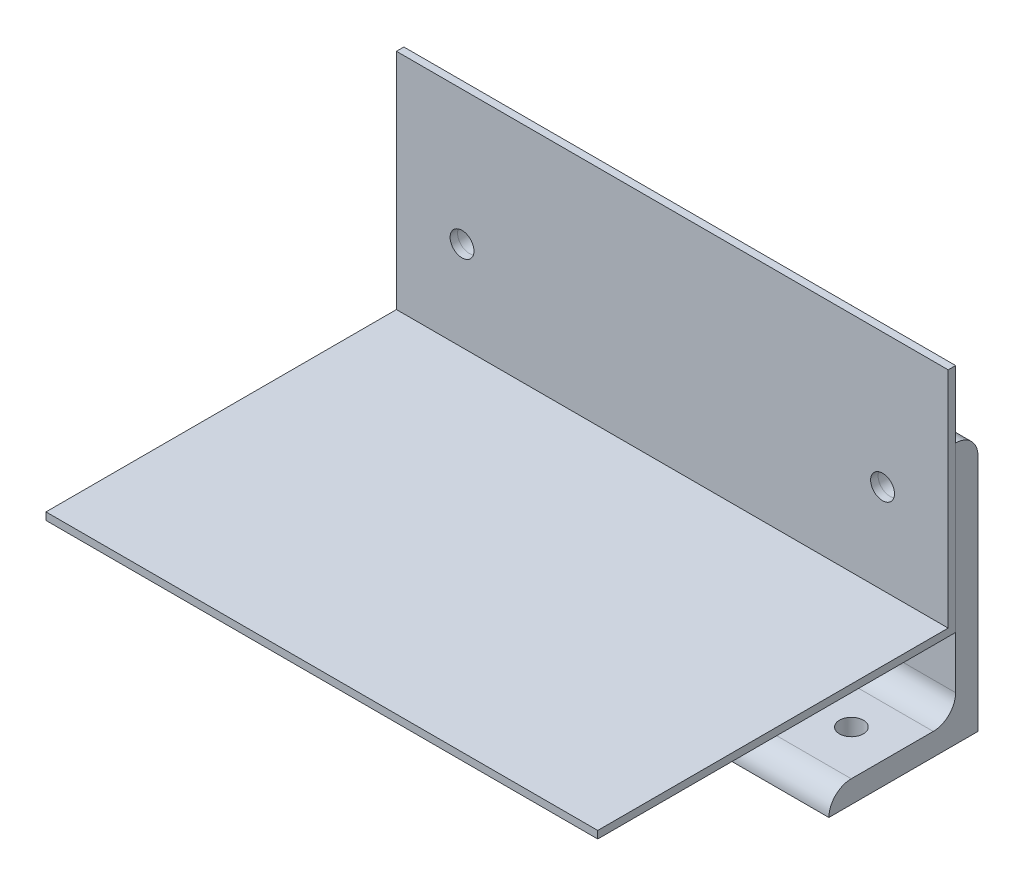
SolidWorks part; units mm, degrees
ref_plane "Спереди" through (0, 0, 0) normal (0, 0, 1) x (1, 0, 0)
ref_plane "Сверху" through (0, 0, 0) normal (0, 1, 0) x (1, 0, 0)
ref_plane "Справа" through (0, 0, 0) normal (1, 0, 0) x (0, 0, -1)
sketch "Эскиз1" plane through (0, 0, 0) normal (1, 0, 0) x (0, 0, -1)
  line L1 (0, 0) -> (-48, 0)
  line L2 (0, 0) -> (0, 31)
  line L3 (0, 31) -> (-1, 31)
  line L4 (-48, 0) -> (-48, 1)
  line L7 (-48, 1) -> (-1, 1)
  line L8 (-1, 31) -> (-1, 1)
  dimension "D1" = 1
  dimension "D2" = 31
  dimension "D3" = 48
  dimension "D4" = 1
extrude "Бобышка-Вытянуть1" add sketch "Эскиз1" along normal blind 74
sketch "Эскиз2" plane through (0, 0, 0) normal (0, 0, -1) x (-1, 0, 0)
  line L0 (-74, 31) -> (0, 31) construction
  line L1 (-74, 0) -> (-74, 31) construction
  line L2 (0, 0) -> (0, 31) construction
  circle A0 centre (-65.2, 13) radius 1.6
  circle A1 centre (-8.8, 13) radius 1.6
  dimension "D1" = 3.2
  dimension "D2" = 3.2
  dimension "D3" = 18
  dimension "D4" = 8.8
  dimension "D5" = 8.8
extrude "Вырез-Вытянуть1" cut sketch "Эскиз2" against normal blind 13
sketch "Sketch2" plane through (0, 0, 0) normal (0, 0, -1) x (-1, 0, 0)
  line L0 (-74, 0) -> (-74, 31) construction
  line L1 (-74, 22) -> (0, 22)
  line L2 (-74, 22) -> (-74, -10)
  line L3 (-74, -10) -> (0, -10)
  line L4 (0, 22) -> (0, -10)
  line L5 (0, 0) -> (0, 31) construction
  line L6 (-74, 0) -> (0, 0) construction
  circle A0 centre (-65.2, 13) radius 1.6 construction
  dimension "D1" = 9
  dimension "D2" = 10
extrude "Boss-Extrude1" add sketch "Sketch2" along normal blind 3 separate body
sketch "Sketch3" plane through (0, -10, 0) normal (0, -1, 0) x (1, 0, 0)
  line L0 (74, 48) -> (74, 0) construction
  line L1 (0, -3) -> (74, -3)
  line L2 (0, -3) -> (0, 17)
  line L3 (0, 17) -> (74, 17)
  line L4 (74, -3) -> (74, 17)
  circle A0 centre (6, 7.9797) radius 1.6
  circle A1 centre (68, 7.9797) radius 1.6
  dimension "D2" = 3.2
  dimension "D4" = 6
  dimension "D5" = 6
  dimension "D1" = 20
  dimension "D3" = 2
extrude "Boss-Extrude2" add sketch "Sketch3" along normal blind 3
sketch "Sketch5" plane through (0, 0, -3) normal (0, 0, -1) x (-1, 0, 0)
  circle A0 centre (-65.2, 13) radius 1.6 construction
  circle A1 centre (-8.8, 13) radius 1.6 construction
  circle A2 centre (-65.2, 13) radius 1.6
  circle A3 centre (-8.8, 13) radius 1.6
extrude "Cut-Extrude1" cut sketch "Sketch5" against normal blind 3
fillet "Fillet3" radius 3 1 edges at (37, 22, -3)
fillet "Fillet5" radius 3 1 edges at (37, -10, 17)
fillet "Fillet6" radius 3 1 edges at (37, -10, 0)
